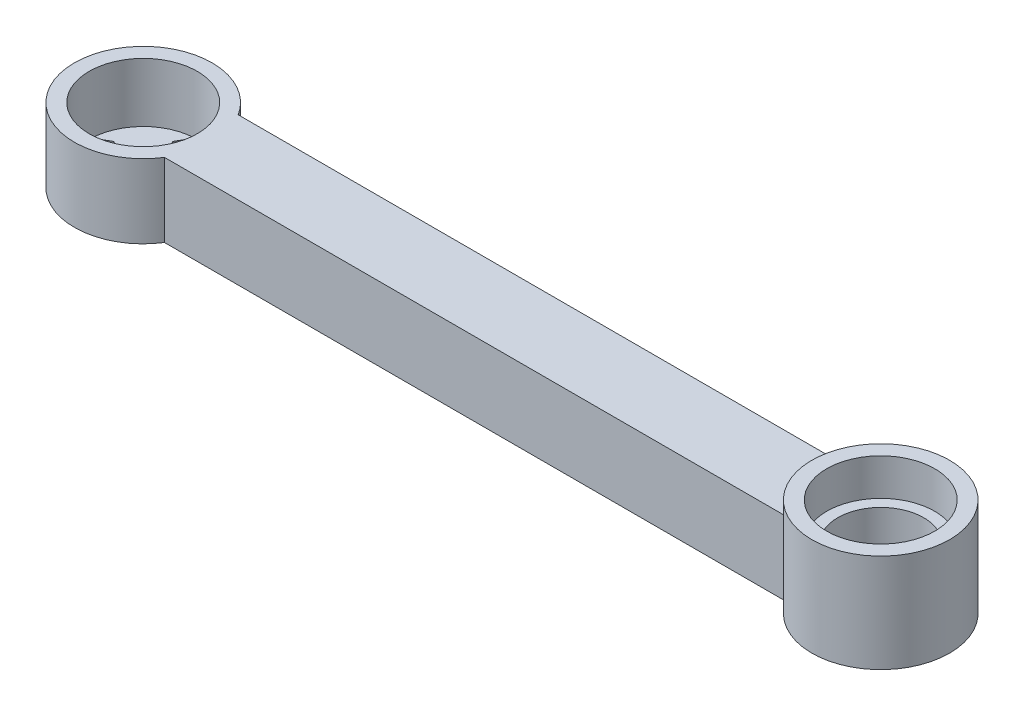
SolidWorks part; units mm, degrees
note: The reader was unsure of these and kept them because the rebuilt part matched: shared geometry of "Sketch2<12>", "Sketch2<9>", "Sketch2<11>".
ref_plane "Front Plane" through (0, 0, 0) normal (0, 0, 1) x (1, 0, 0)
ref_plane "Top Plane" through (0, 0, 0) normal (0, 1, 0) x (1, 0, 0)
ref_plane "Right Plane" through (0, 0, 0) normal (1, 0, 0) x (0, 0, -1)
sketch "Sketch2" plane through (0, 0, 0) normal (0, 1, 0) x (1, 0, 0)
  circle A0 centre (-50, 3.2206) radius 14
  circle A1 centre (100, 3.2206) radius 14
  circle A2 centre (100, 3.2206) radius 11
  circle A3 centre (100, 3.2206) radius 8.75
  circle A4 centre (-50, 3.2206) radius 11
  dimension "D1" = 28
  dimension "D2" = 28
  dimension "D3" = 22
  dimension "D4" = 3
  dimension "D5" = 17.5
  dimension "D6" = 22
extrude "Boss-Extrude7" add sketch "Sketch2" along normal blind 15 contours A0
extrude "Boss-Extrude10" add sketch "Sketch2<12>" along normal blind 3 contours A4
sketch "Sketch2<12>" plane through (0, 0, 0) normal (0, 1, 0) x (1, 0, 0) same geometry as "Sketch2"
extrude "Boss-Extrude8" add sketch "Sketch2<9>" along normal blind 20 separate body contours A1
sketch "Sketch2<9>" plane through (0, 0, 0) normal (0, 1, 0) x (1, 0, 0) same geometry as "Sketch2"
extrude "Boss-Extrude9" add sketch "Sketch2<11>" along normal blind 12.5 contours A2 A3
sketch "Sketch2<11>" plane through (0, 0, 0) normal (0, 1, 0) x (1, 0, 0) same geometry as "Sketch2"
sketch "Sketch3" plane through (0, 0, 0) normal (1, 0, 0) x (0, 0, -1)
  line L1 (10.7206, 15) -> (-4.2794, 15)
  line L2 (10.7206, 15) -> (10.7206, 0)
  line L3 (10.7206, 0) -> (-4.2794, 0)
  line L4 (-4.2794, 15) -> (-4.2794, 0)
  line L6 (17.2206, 0) -> (17.2206, 15) construction
  line L7 (-1.2794, 12) -> (7.7206, 12)
  line L8 (-1.2794, 12) -> (-1.2794, 0)
  line L9 (-1.2794, 0) -> (7.7206, 0)
  line L10 (7.7206, 12) -> (7.7206, 0)
  line L11 (-10.7794, 15) -> (-10.7794, 0) construction
  dimension "D1" = 15
  dimension "D2" = 15
  dimension "D3" = 6.5
  dimension "D4" = 6.5
  dimension "D5" = 9
  dimension "D6" = 12
  dimension "D7" = 0
  dimension "D8" = 3
  dimension "D9" = 3
  dimension "D10" = 3
extrude "Boss-Extrude11" add sketch "Sketch3" against normal up to body and the other way up to body separate body contours L7 L10 L3 L2 L1 L4 L8
sketch "Sketch10" plane through (0, 3, 0) normal (0, 1, 0) x (1, 0, 0)
  line L0 (-50, 17.2454) -> (-50, -10.8226) construction
  line L1 (-47.85, 11.3587) -> (-48.925, 13.2206)
  line L2 (-48.925, 13.2206) -> (-51.075, 13.2206)
  line L3 (-51.075, 13.2206) -> (-52.15, 11.3587)
  line L4 (-52.15, 11.3587) -> (-51.075, 9.4967)
  line L5 (-51.075, 9.4967) -> (-48.925, 9.4967)
  line L6 (-48.925, 9.4967) -> (-47.85, 11.3587)
  line L7 (-80, 3.2206) -> (-20, 3.2206) construction
  line L33 (-58.138, 5.3706) -> (-60, 4.2956)
  line L34 (-60, 4.2956) -> (-60, 2.1456)
  line L35 (-60, 2.1456) -> (-58.138, 1.0706)
  line L36 (-58.138, 1.0706) -> (-56.2761, 2.1456)
  line L37 (-56.2761, 2.1456) -> (-56.2761, 4.2956)
  line L38 (-56.2761, 4.2956) -> (-58.138, 5.3706)
  line L39 (-41.862, 5.3706) -> (-43.7239, 4.2956)
  line L40 (-43.7239, 4.2956) -> (-43.7239, 2.1456)
  line L41 (-43.7239, 2.1456) -> (-41.862, 1.0706)
  line L42 (-41.862, 1.0706) -> (-40, 2.1456)
  line L43 (-40, 2.1456) -> (-40, 4.2956)
  line L44 (-40, 4.2956) -> (-41.862, 5.3706)
  line L45 (-47.85, -4.9174) -> (-48.925, -3.0555)
  line L46 (-48.925, -3.0555) -> (-51.075, -3.0555)
  line L47 (-51.075, -3.0555) -> (-52.15, -4.9174)
  line L48 (-52.15, -4.9174) -> (-51.075, -6.7794)
  line L49 (-51.075, -6.7794) -> (-48.925, -6.7794)
  line L50 (-48.925, -6.7794) -> (-47.85, -4.9174)
  circle A0 centre (-50, 11.3587) radius 1.862 construction
  circle A1 centre (-58.138, 3.2206) radius 1.862 construction
  circle A2 centre (-41.862, 3.2206) radius 1.862 construction
  circle A3 centre (-50, 3.2206) radius 11 construction
  circle A4 centre (-50, -4.9174) radius 1.862 construction
  circle A6 centre (-50, 3.2206) radius 11 construction
  point P1 (-50, 13.2206)
  point P14 (-50, 3.2114)
  point P15 (0, 0)
  point P17 (-50, 3.2206)
  dimension "D2" = 10
  dimension "D1" = 4.3
  dimension "D3" = 4.3
  dimension "D4" = 4.3
  dimension "D5" = 4.3
  dimension "D6" = 10
  dimension "D7" = 10
  dimension "D8" = 10
extrude "Cut-Extrude6" cut sketch "Sketch10" against normal blind 1.1 contours L39 L40 L41 L42 L43 L44 | L1 L2 L3 L4 L5 L6 | L33 L34 L35 L36 L37 L38 | L45 L46 L47 L48 L49 L50
sketch "Sketch13" plane through (0, 3, 0) normal (0, 1, 0) x (1, 0, 0)
  circle A0 centre (-50, 11.3587) radius 1.15
  circle A1 centre (-41.862, 3.2206) radius 1.15
  circle A2 centre (-50, -4.9174) radius 1.15
  circle A3 centre (-58.138, 3.2206) radius 1.15
  dimension "D1" = 2.3
  dimension "D2" = 2.3
  dimension "D3" = 2.3
  dimension "D4" = 2.3
extrude "Cut-Extrude7" cut sketch "Sketch13" against normal blind 3
sketch "Sketch15" plane through (0, 0, -7.7206) normal (0, 0, 1) x (1, 0, 0)
  line L0 (-36.7429, 0) -> (86.7429, 0) construction
  line L1 (-15.307, 12) -> (-12.307, 12)
  line L2 (-15.307, 12) -> (-15.307, 2.5)
  line L3 (-15.307, 2.5) -> (-12.307, 2.5)
  line L4 (-12.307, 12) -> (-12.307, 2.5)
  line L6 (88.1784, 0) -> (88.1784, 15) construction
  line L8 (13.5643, 12) -> (10.5643, 12)
  line L9 (13.5643, 12) -> (13.5643, 2.5)
  line L10 (13.5643, 2.5) -> (10.5643, 2.5)
  line L11 (10.5643, 12) -> (10.5643, 2.5)
  line L12 (36.4357, 12) -> (39.4357, 12)
  line L13 (36.4357, 12) -> (36.4357, 2.5)
  line L14 (36.4357, 2.5) -> (39.4357, 2.5)
  line L15 (39.4357, 12) -> (39.4357, 2.5)
  line L16 (62.307, 12) -> (65.307, 12)
  line L17 (62.307, 12) -> (62.307, 2.5)
  line L18 (62.307, 2.5) -> (65.307, 2.5)
  line L19 (65.307, 12) -> (65.307, 2.5)
  line L20 (-38.1784, 15) -> (-38.1784, 0) construction
  point P22 (12.0643, 2.5)
  dimension "D1" = 3
  dimension "D2" = 9.5
  dimension "D3" = 2.5
  dimension "D4" = 22.8714
  dimension "D5" = 22.8714
  dimension "D6" = 3
  dimension "D7" = 9.5
  dimension "D8" = 3
  dimension "D9" = 9.5
  dimension "D10" = 3
  dimension "D11" = 9.5
  dimension "D12" = 2.5
  dimension "D13" = 2.5
  dimension "D14" = 2.5
  dimension "D15" = 22.8714
  dimension "D16" = 22.8714
  dimension "D17" = 22.8714
extrude "Boss-Extrude12" add sketch "Sketch15" along normal up to next
fillet "Fillet1" radius 2 16 edges at (65.307, 7.25, -7.7206) (65.307, 7.25, 1.2794) (62.307, 7.25, -7.7206) (62.307, 7.25, 1.2794) (39.4357, 7.25, -7.7206) (39.4357, 7.25, 1.2794) (36.4357, 7.25, -7.7206) (36.4357, 7.25, 1.2794) (13.5643, 7.25, -7.7206) (13.5643, 7.25, 1.2794) (10.5643, 7.25, -7.7206) (10.5643, 7.25, 1.2794) (-12.307, 7.25, -7.7206) (-12.307, 7.25, 1.2794) (-15.307, 7.25, -7.7206) (-15.307, 7.25, 1.2794)
